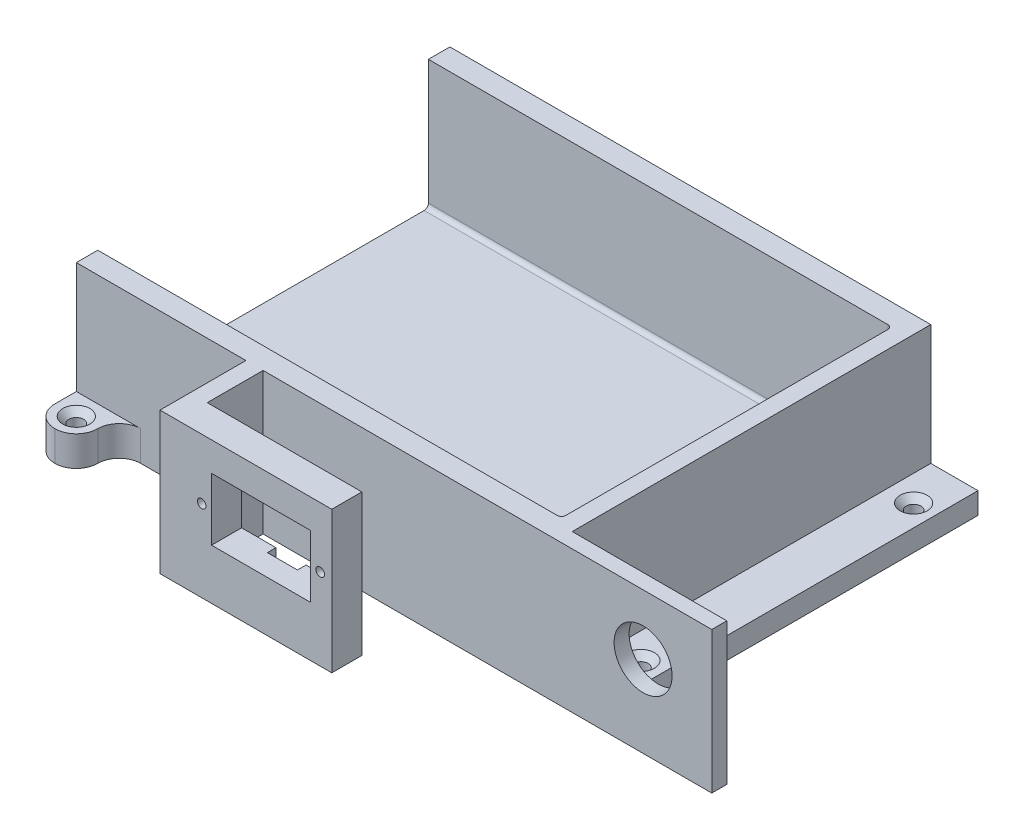
SolidWorks part; units mm, degrees
ref_plane "Plan de face" through (0, 0, 0) normal (0, 0, 1) x (1, 0, 0)
ref_plane "Plan de dessus" through (0, 0, 0) normal (0, 1, 0) x (1, 0, 0)
ref_plane "Plan de droite" through (0, 0, 0) normal (1, 0, 0) x (0, 0, -1)
sketch "Esquisse1" plane through (0, 0, 0) normal (0, 1, 0) x (1, 0, 0)
  line L1 (0, 0) -> (138, 0)
  line L2 (0, 0) -> (0, 77)
  line L3 (0, 77) -> (138, 77)
  line L4 (138, 0) -> (138, 77)
  dimension "D1" = 138
  dimension "D2" = 77
extrude "Boss.-Extru.1" add sketch "Esquisse1" along normal blind 3
sketch "Esquisse2" plane through (0, 3, 0) normal (0, 1, 0) x (1, 0, 0)
  line L0 (0, 0) -> (138, 0) construction
  line L6 (138, 77) -> (123, 77)
  line L7 (138, 77) -> (138, 0)
  line L8 (138, 0) -> (123, 0)
  line L9 (123, 77) -> (123, 0)
  dimension "D1" = 15
extrude "Boss.-Extru.2" add sketch "Esquisse2" along normal blind 30
fillet "Congé1" radius 13.85 1 edges at (123, 3, -38.5)
sketch "Esquisse3" plane through (0, 0, -77) normal (0, 0, -1) x (-1, 0, 0)
  line L0 (-138, 33) -> (-123, 33) construction
  line L1 (-138, 0) -> (0, 0)
  line L2 (-138, 0) -> (-138, 33)
  line L3 (-138, 33) -> (0, 33)
  line L4 (0, 0) -> (0, 33)
extrude "Boss.-Extru.3" add sketch "Esquisse3" along normal blind 5
ref_plane "Plan1" through (0, 0, -38.5) normal (0, 0, 1) x (1, 0, 0)
mirror "Symétrie1" about plane through (0, 0, -38.5) normal (0, 0, 1) of "Boss.-Extru.3"
sketch "Esquisse26" plane through (0, 0, 5) normal (0, 0, 1) x (1, 0, 0)
  line L0 (0, 33) -> (138, 33) construction
  line L1 (0, 0) -> (15, 0)
  line L2 (0, 0) -> (0, 33)
  line L3 (0, 33) -> (15, 33)
  line L4 (15, 0) -> (15, 33)
  dimension "D1" = 15
extrude "Enlèv. mat.-Extru.13" cut sketch "Esquisse26" against normal up to surface (87 mm away) up to face at (69, 16.5, -82)
fillet "Congé5" radius 1 6 edges at (123, 24.925, 0) (118.9434, 7.0566, 0) (123, 24.925, -77) (118.9434, 7.0566, -77) (62.075, 3, 0) (62.075, 3, -77)
sketch "Esquisse27" plane through (0, 0, 5) normal (0, 0, 1) x (1, 0, 0)
  line L0 (138, 0) -> (15, 0) construction
  line L1 (15, 33) -> (19, 33)
  line L2 (15, 33) -> (15, 0)
  line L3 (15, 0) -> (19, 0)
  line L4 (19, 33) -> (19, 0)
  dimension "D1" = 4
extrude "Boss.-Extru.6" [suppressed] add sketch "Esquisse27" along normal blind 34
sketch "Esquisse28" plane through (0, 0, 0) normal (0, -1, 0) x (1, 0, 0)
  line L1 (15, 5) -> (19, 5)
  line L2 (15, 5) -> (15, 48.5)
  line L3 (15, 48.5) -> (39, 48.5)
  line L4 (19, 5) -> (19, 45)
  line L7 (19, 45) -> (39, 45)
  line L8 (39, 48.5) -> (39, 45)
  dimension "D1" = 43.5
  dimension "D2" = 3.5
  dimension "D3" = 20
  dimension "D4" = 4
extrude "Boss.-Extru.7" [suppressed] add sketch "Esquisse28" against normal blind 33
sketch "Esquisse29" [suppressed] plane through (0, 0, 48.5) normal (0, 0, 1) x (1, 0, 0)
  line L0 (39, 33) -> (39, 0) construction
  line L2 (39, 0) -> (15, 0) construction
  line L3 (15, 33) -> (138, 33) construction
  circle A0 centre (29, 19) radius 6
  dimension "D1" = 12
  dimension "D2" = 10
  dimension "D3" = 19
extrude "Enlèv. mat.-Extru.14" [suppressed] cut sketch "Esquisse29" against normal up to surface (3.5 mm away)
sketch "Esquisse33" plane through (0, 33, 0) normal (0, 1, 0) x (1, 0, 0)
  line L0 (15, -5) -> (138, -5) construction
  line L1 (138, 82) -> (127, 82)
  line L2 (138, 82) -> (138, -1.5)
  line L3 (138, -1.5) -> (127, -1.5)
  line L4 (127, 82) -> (127, -1.5)
  line L5 (123, 76) -> (123, 1) construction
  dimension "D1" = 3.5
  dimension "D2" = 4
extrude "Enlèv. mat.-Extru.15" cut sketch "Esquisse33" against normal offset from surface (28 mm away) 5 up to face at (76.5, 0, -38.5)
sketch "Esquisse34" plane through (138, 0, 0) normal (1, 0, 0) x (0, 0, -1)
  line L0 (-1.5, 5) -> (-1.5, 33) construction
  line L1 (-1.5, 0) -> (-5, 0)
  line L2 (-1.5, 0) -> (-1.5, 33)
  line L3 (-1.5, 33) -> (-5, 33)
  line L4 (-5, 0) -> (-5, 33)
extrude "Boss.-Extru.8" add sketch "Esquisse34" along normal blind 25
sketch "Esquisse43" plane through (0, 0, 0) normal (0, -1, 0) x (1, 0, 0)
  line L0 (163, 5) -> (15, 5) construction
  line L1 (54.5, 5) -> (58.5, 5)
  line L2 (54.5, 5) -> (54.5, 25)
  line L3 (54.5, 25) -> (94.5, 25)
  line L4 (58.5, 5) -> (58.5, 18)
  line L5 (15, -82) -> (15, 5) construction
  line L8 (58.5, 18) -> (94.5, 18)
  line L9 (94.5, 25) -> (94.5, 18)
  point P1 (56.5, 5)
  dimension "D1" = 4
  dimension "D2" = 20
  dimension "D3" = 7
  dimension "D4" = 36
  dimension "D5" = 41.5
extrude "Boss.-Extru.11" add sketch "Esquisse43" against normal up to surface (33 mm away) up to face at (94.2012, 33, -31.8333)
sketch "Esquisse35" plane through (0, 0, 25) normal (0, 0, 1) x (1, 0, 0)
  line L1 (66.5, 26.25) -> (89.5, 26.25)
  line L2 (66.5, 26.25) -> (66.5, 11.75)
  line L3 (66.5, 11.75) -> (89.5, 11.75)
  line L4 (89.5, 26.25) -> (89.5, 11.75)
  line L5 (94.5, 33) -> (94.5, 0) construction
  line L7 (94.5, 0) -> (54.5, 0) construction
  circle A0 centre (91.8, 19) radius 1
  circle A1 centre (64.2, 19) radius 1
  point P4 (89.5, 19)
  dimension "D8" = 2
  dimension "D9" = 2
  dimension "D1" = 5
  dimension "D2" = 23
  dimension "D3" = 14.5
  dimension "D4" = 2.3
  dimension "D5" = 7.25
  dimension "D6" = 2.3
  dimension "D7" = 7.25
  dimension "D10" = 19
extrude "Enlèv. mat.-Extru.16" cut sketch "Esquisse35" against normal up to surface (7 mm away) up to face at (76.5, 16.5, 18)
sketch "Esquisse36" plane through (0, 0, 18) normal (0, 0, -1) x (-1, 0, 0)
  line L0 (-89.5, 11.75) -> (-66.5, 11.75) construction
  line L1 (-81.5, 11.75) -> (-74.5, 11.75)
  line L2 (-81.5, 11.75) -> (-81.5, 0)
  line L3 (-81.5, 0) -> (-74.5, 0)
  line L4 (-74.5, 11.75) -> (-74.5, 0)
  line L5 (-89.5, 26.25) -> (-89.5, 11.75) construction
  line L6 (-163, 0) -> (-138, 0) construction
  dimension "D1" = 8
  dimension "D2" = 7
extrude "Enlèv. mat.-Extru.17" cut sketch "Esquisse36" against normal blind 2
sketch "Esquisse44" plane through (0, 0, 5) normal (0, 0, 1) x (1, 0, 0)
  line L0 (58.5, 33) -> (163, 33) construction
  line L1 (163, 33) -> (163, 0) construction
  circle A0 centre (147, 19) radius 6
  dimension "D2" = 12
  dimension "D1" = 14
  dimension "D3" = 16
extrude "Enlèv. mat.-Extru.19" cut sketch "Esquisse44" against normal up to surface (3.5 mm away) up to face at (142.6667, 12.6667, 1.5)
hole_wizard "Dégagement M124" positions "Esquisse47" profile "Esquisse46" hole size "M12" standard "ISO"
sketch "Esquisse47" plane through (0, 0, 5) normal (0, 0, 1) x (1, 0, 0)
  point P0 (147, 19)
sketch "Esquisse46" plane through (147, 19, 5) normal (1, 0, 0) x (0, -1, 0)
  line L0 (0, 0) -> (0, 7.5558)
  line L1 (0, 7.5558) -> (6.75, 3.5)
  line L2 (6.75, 3.5) -> (6.75, 0)
  line L5 (6.75, 0) -> (0, 0)
  line L10 (0, 7.5558) -> (-6.75, 3.5) construction
  line L11 (0, -6.35) -> (0, 107.95) construction
  dimension "Diamètre du perçage" = 13.5
  dimension "Profondeur du perçage" = 3.5
  dimension "Angle de pointe" = 118
sketch "Esquisse48" plane through (0, 5, 0) normal (0, 1, 0) x (1, 0, 0)
  line L0 (138, -1.5) -> (138, 82) construction
  line L1 (127, -1.5) -> (138, -1.5) construction
  line L2 (138, 82) -> (127, 82) construction
  circle A0 centre (133, 8.5) radius 1.5
  circle A2 centre (133, 72) radius 1.5
  dimension "D1" = 3
  dimension "D3" = 3
  dimension "D4" = 5
  dimension "D6" = 5
  dimension "D7" = 10
  dimension "D8" = 10
extrude "Enlèv. mat.-Extru.20" cut sketch "Esquisse48" against normal up to surface (5 mm away) up to face at (84.9375, 0, 1.3125)
hole_wizard "Fraisage pour vis à tête fraisée M32" positions "Esquisse51" profile "Esquisse50" countersink size "M3" standard "ISO"
sketch "Esquisse51" plane through (0, 5, 0) normal (0, 1, 0) x (1, 0, 0)
  point P0 (133, 72)
  point P6 (133, 8.5)
  point P10 (0, 0)
sketch "Esquisse50" plane through (133, 5, -72) normal (1, 0, 0) x (0, 0, 1)
  line L0 (0, 0) -> (0, 6.0215)
  line L1 (0, 6.0215) -> (1.7, 5)
  line L2 (1.7, 5) -> (1.7, 1.45)
  line L3 (1.7, 1.45) -> (3.15, 0)
  line L5 (3.15, 0) -> (0, 0)
  line L6 (-1.7, 1.45) -> (-3.15, 0) construction
  line L10 (0, 6.0215) -> (-1.7, 5) construction
  line L11 (0, -6.35) -> (0, 107.95) construction
  dimension "Diamètre du perçage" = 3.4
  dimension "Profondeur du perçage" = 5
  dimension "Diamètre du fraisage entrant" = 6.3
  dimension "Angle du fraisage entrant" = 90
  dimension "Angle de pointe" = 118
sketch "Esquisse37" plane through (15, 0, 0) normal (-1, 0, 0) x (0, 0, 1)
  line L0 (-82, 0) -> (5, 0) construction
  line L1 (-77, 0) -> (-107, 0)
  line L2 (-77, 0) -> (-77, 68)
  line L3 (-77, 68) -> (-107, 68)
  line L4 (-107, 0) -> (-107, 68)
  line L5 (-77, 4) -> (-77, 33) construction
  line L6 (-82, 33) -> (-77, 33) construction
  dimension "D1" = 30
  dimension "D2" = 35
extrude "Boss.-Extru.9" [suppressed] add sketch "Esquisse37" against normal blind 3.5
sketch "Esquisse38" [suppressed] plane through (15, 0, 0) normal (-1, 0, 0) x (0, 0, 1)
  line L0 (-77, 68) -> (-107, 68) construction
  line L1 (-107, 68) -> (-107, 0) construction
  circle A0 centre (-94.5, 54) radius 6
  dimension "D3" = 12
  dimension "D1" = 14
  dimension "D2" = 12.5
extrude "Enlèv. mat.-Extru.18" [suppressed] cut sketch "Esquisse38" against normal up to surface (3.5 mm away)
hole_wizard "Dégagement M122" [suppressed] positions "Esquisse30" profile "Esquisse32" hole size "M12" standard "ISO"
sketch "Esquisse30" [suppressed] plane through (0, 0, 48.5) normal (0, 0, 1) x (1, 0, 0)
  point P0 (29, 19)
sketch "Esquisse32" plane through (29, 19, 48.5) normal (1, 0, 0) x (0, -1, 0)
  line L0 (0, 0) -> (0, 7.5558)
  line L1 (0, 7.5558) -> (6.75, 3.5)
  line L2 (6.75, 3.5) -> (6.75, 0)
  line L5 (6.75, 0) -> (0, 0)
  line L10 (0, 7.5558) -> (-6.75, 3.5) construction
  line L11 (0, -6.35) -> (0, 107.95) construction
  dimension "Diamètre du perçage" = 13.5
  dimension "Profondeur du perçage" = 3.5
  dimension "Angle de pointe" = 118
hole_wizard "Dégagement M123" [suppressed] positions "Esquisse39" profile "Esquisse40" hole size "M12" standard "ISO"
sketch "Esquisse39" [suppressed] plane through (15, 0, 0) normal (-1, 0, 0) x (0, 0, 1)
  point P0 (-94.5, 54)
sketch "Esquisse40" plane through (15, 54, -94.5) normal (0, 1, 0) x (0, 0, 1)
  line L0 (0, 0) -> (0, 7.5558)
  line L1 (0, 7.5558) -> (6.75, 3.5)
  line L2 (6.75, 3.5) -> (6.75, 0)
  line L5 (6.75, 0) -> (0, 0)
  line L10 (0, 7.5558) -> (-6.75, 3.5) construction
  line L11 (0, -6.35) -> (0, 107.95) construction
  dimension "Diamètre du perçage" = 13.5
  dimension "Profondeur du perçage" = 3.5
  dimension "Angle de pointe" = 118
sketch "Esquisse42" [suppressed] plane through (0, 0, 0) normal (0, -1, 0) x (1, 0, 0)
  line L0 (18.5, -107) -> (18.5, -82)
  line L1 (18.5, -107) -> (28.5, -107)
  line L2 (18.5, -82) -> (28.5, -82)
  line L3 (28.5, -107) -> (28.5, -82)
  dimension "D1" = 10
extrude "Boss.-Extru.10" [suppressed] add sketch "Esquisse42" against normal blind 5
fillet "Congé6" [suppressed] radius 1
fillet "Congé7" [suppressed] radius 10
sketch "Esquisse4" [suppressed] plane through (0, 0, 0) normal (-1, 0, 0) x (0, 0, 1)
  line L1 (0, 33) -> (-25, 33)
  line L2 (0, 33) -> (0, 13)
  line L3 (0, 13) -> (-25, 13)
  line L4 (-25, 33) -> (-25, 13)
  dimension "D1" = 25
  dimension "D2" = 20
extrude "Enlèv. mat.-Extru.1" [suppressed] cut sketch "Esquisse4" against normal blind 6
sketch "Esquisse5" [suppressed] plane through (0, 33, 0) normal (0, 1, 0) x (1, 0, 0)
  line L0 (123, 76) -> (123, 1) construction
  line L1 (138, 82) -> (128, 82)
  line L2 (138, 82) -> (138, 3.5)
  line L3 (138, 3.5) -> (128, 3.5)
  line L4 (128, 82) -> (128, 3.5)
  line L5 (113, 0) -> (138, 0) construction
  dimension "D1" = 5
  dimension "D2" = 3.5
extrude "Enlèv. mat.-Extru.2" [suppressed] cut sketch "Esquisse5" against normal blind 30
sketch "Esquisse6" [suppressed] plane through (0, 0, 0) normal (0, 0, 1) x (1, 0, 0)
  line L0 (113, 33) -> (138, 33) construction
  line L3 (138, 33) -> (138, 0) construction
  circle A0 centre (125.5, 21) radius 6.25
  dimension "D3" = 12.5
  dimension "D1" = 12
  dimension "D2" = 12.5
extrude "Enlèv. mat.-Extru.3" [suppressed] cut sketch "Esquisse6" against normal up to surface (3.5 mm away)
sketch "Esquisse7" [suppressed] plane through (0, 0, -80) normal (0, 0, -1) x (-1, 0, 0)
  line L1 (-138, 0) -> (-118, 0)
  line L2 (-138, 0) -> (-138, 3)
  line L3 (-138, 3) -> (-118, 3)
  line L4 (-118, 0) -> (-118, 3)
extrude "Enlèv. mat.-Extru.4" [suppressed] cut sketch "Esquisse7" against normal blind 30
sketch "Esquisse8" [suppressed] plane through (0, 33, 0) normal (0, 1, 0) x (1, 0, 0)
  line L0 (99.15, 0) -> (99.15, 75) construction
  line L1 (118, 80) -> (99.15, 80)
  line L2 (118, 80) -> (118, 50)
  line L3 (118, 50) -> (99.15, 50)
  line L4 (99.15, 80) -> (99.15, 50)
  dimension "D1" = 30
extrude "Enlèv. mat.-Extru.5" [suppressed] cut sketch "Esquisse8" against normal up to surface (33 mm away)
sketch "Esquisse10" [suppressed] plane through (118, 0, 0) normal (1, 0, 0) x (0, 0, -1)
  line L0 (50, 3) -> (3.5, 3) construction
  line L1 (15.5, 3) -> (23.5, 3)
  line L2 (15.5, 3) -> (15.5, 18)
  line L3 (15.5, 18) -> (23.5, 18)
  line L4 (23.5, 3) -> (23.5, 18)
  dimension "D1" = 12
  dimension "D2" = 8
  dimension "D3" = 15
extrude "Enlèv. mat.-Extru.6" [suppressed] cut sketch "Esquisse10" against normal offset from surface (3 mm away) 2
sketch "Esquisse11" [suppressed] plane through (0, 3, 0) normal (0, 1, 0) x (1, 0, 0)
  line L1 (115, 23.5) -> (118, 23.5)
  line L2 (115, 23.5) -> (115, 15.5)
  line L3 (115, 15.5) -> (131, 15.5)
  line L8 (138, 3.5) -> (131, 3.5)
  line L9 (131, 15.5) -> (131, 3.5)
  line L10 (138, 50) -> (138, 3.5)
  line L11 (118, 50) -> (138, 50)
  line L12 (118, 50) -> (118, 23.5)
  dimension "D1" = 12
  dimension "D2" = 7
  dimension "D3" = 20
extrude "Enlèv. mat.-Extru.7" [suppressed] cut sketch "Esquisse11" against normal up to surface (3 mm away)
sketch "Esquisse12" [suppressed] plane through (0, 0, 0) normal (-1, 0, 0) x (0, 0, 1)
  line L1 (-80, 33) -> (0, 33)
  line L2 (-80, 33) -> (-80, 0)
  line L3 (-80, 0) -> (0, 0)
  line L4 (0, 33) -> (0, 0)
extrude "Enlèv. mat.-Extru.8" [suppressed] cut sketch "Esquisse12" against normal blind 2
sketch "Esquisse13" [suppressed] plane through (0, 0, 0) normal (0, 0, 1) x (1, 0, 0)
  line L0 (37, 0) -> (44.5969, -20)
  line L1 (2, 0) -> (138, 0) construction
  line L2 (44.5969, -20) -> (71.5969, -20)
  line L3 (71.5969, -20) -> (78, 0)
  line L4 (78, 0) -> (37, 0)
  line L7 (113, 33) -> (113, 16.85) construction
  dimension "D1" = 35
  dimension "D2" = 27
  dimension "D3" = 35
  dimension "D4" = 20
  dimension "D5" = 21
extrude "Boss.-Extru.4" [suppressed] add sketch "Esquisse13" against normal blind 7
sketch "Esquisse14" [suppressed] plane through (0, 0, 0) normal (0, 0, 1) x (1, 0, 0)
  line L0 (44.5969, -20) -> (71.5969, -20) construction
  line L1 (46.5, -2.5) -> (69.5, -2.5)
  line L2 (46.5, -2.5) -> (46.5, -17)
  line L3 (46.5, -17) -> (69.5, -17)
  line L4 (69.5, -2.5) -> (69.5, -17)
  dimension "D1" = 23
  dimension "D2" = 9.5
  dimension "D3" = 3
  dimension "D4" = 14.5
extrude "Enlèv. mat.-Extru.9" [suppressed] cut sketch "Esquisse14" against normal up to surface (7 mm away)
fillet "Congé2" [suppressed] radius 10
sketch "Esquisse15" [suppressed] plane through (2, 0, 0) normal (-1, 0, 0) x (0, 0, 1)
  line L0 (0, 33) -> (-80, 33) construction
  line L1 (-42.9875, 33) -> (-35.9875, 33)
  line L2 (-42.9875, 33) -> (-42.9875, 13)
  line L3 (-42.9875, 13) -> (-35.9875, 13)
  line L4 (-35.9875, 33) -> (-35.9875, 13)
  dimension "D1" = 20
  dimension "D2" = 7
extrude "Boss.-Extru.5" [suppressed] add sketch "Esquisse15" along normal blind 45
sketch "Esquisse16" [suppressed] plane through (0, 0, -35.9875) normal (0, 0, 1) x (1, 0, 0)
  line L0 (-20.5, 33) -> (-20.5, 13) construction
  line L1 (-43, 33) -> (2, 33) construction
  line L2 (-43, 13) -> (2, 13) construction
  line L3 (-43, 23) -> (2, 23) construction
  line L4 (-43, 13) -> (-43, 33) construction
  line L5 (2, 13) -> (2, 33) construction
  line L7 (-38, 30.5) -> (-15, 30.5)
  line L8 (-38, 30.5) -> (-38, 16)
  line L9 (-38, 16) -> (-15, 16)
  line L10 (-15, 30.5) -> (-15, 16)
  dimension "D1" = 23
  dimension "D2" = 14.5
  dimension "D3" = 2.5
  dimension "D4" = 5
extrude "Enlèv. mat.-Extru.10" [suppressed] cut sketch "Esquisse16" against normal up to surface (7 mm away)
fillet "Congé3" [suppressed] radius 20
fillet "Congé4" [suppressed] radius 2
sketch "Esquisse18" [suppressed] plane through (0, 0, -42.9875) normal (0, 0, -1) x (-1, 0, 0)
  line L0 (15, 16) -> (38, 16) construction
  line L1 (23, 16) -> (30, 16)
  line L2 (23, 16) -> (23, 13)
  line L3 (23, 13) -> (30, 13)
  line L4 (30, 16) -> (30, 13)
  line L6 (41, 13) -> (-2, 13) construction
  dimension "D1" = 8
  dimension "D2" = 8
extrude "Enlèv. mat.-Extru.11" [suppressed] cut sketch "Esquisse18" against normal blind 2
sketch "Esquisse20" [suppressed] plane through (0, 0, -42.9875) normal (0, 0, -1) x (-1, 0, 0)
  line L0 (38, 30.5) -> (15, 30.5) construction
  line L1 (10.4, 25.9) -> (15, 25.9)
  line L2 (10.4, 25.9) -> (10.4, 20.6)
  line L3 (10.4, 20.6) -> (15, 20.6)
  line L4 (15, 25.9) -> (15, 20.6)
  line L5 (38, 25.9) -> (42.6, 25.9)
  line L6 (38, 25.9) -> (38, 20.6)
  line L7 (38, 20.6) -> (42.6, 20.6)
  line L8 (42.6, 25.9) -> (42.6, 20.6)
  line L9 (15, 16) -> (23, 16) construction
  line L10 (15, 30.5) -> (15, 16) construction
  line L11 (38, 16) -> (38, 30.5) construction
  line L12 (30, 16) -> (38, 16) construction
  dimension "D1" = 4.6
  dimension "D2" = 4.6
  dimension "D3" = 4.6
  dimension "D4" = 4.6
  dimension "D5" = 4.6
  dimension "D6" = 4.6
sketch "Esquisse21" [suppressed] plane through (0, 0, -42.9875) normal (0, 0, -1) x (-1, 0, 0)
  line L0 (15, 25.9) -> (15, 20.6) construction
  line L1 (10.4, 25.9) -> (10.4, 20.6) construction
  line L2 (10.4, 23.25) -> (15, 23.25) construction
  line L3 (15, 23.25) -> (42.6, 23.25) construction
  line L4 (42.6, 25.9) -> (42.6, 20.6) construction
  circle A0 centre (12.7, 23.25) radius 1
  circle A1 centre (40.3, 23.25) radius 1
  dimension "D1" = 2
  dimension "D3" = 2
  dimension "D2" = 2.3
extrude "Enlèv. mat.-Extru.12" [suppressed] cut sketch "Esquisse21" against normal up to surface (7 mm away)
hole_wizard "Dégagement M21" [suppressed] positions "Esquisse22" profile "Esquisse23" hole size "M2" standard "ISO"
sketch "Esquisse22" [suppressed] plane through (0, 0, -42.9875) normal (0, 0, -1) x (-1, 0, 0)
  point P0 (40.3, 23.25)
  point P3 (12.7, 23.25)
sketch "Esquisse23" plane through (-40.3, 23.25, -42.9875) normal (1, 0, 0) x (0, 1, 0)
  line L0 (0, 0) -> (0, 10.721)
  line L1 (0, 10.721) -> (1.2, 10)
  line L2 (1.2, 10) -> (1.2, 0)
  line L5 (1.2, 0) -> (0, 0)
  line L10 (0, 10.721) -> (-1.2, 10) construction
  line L11 (0, -6.35) -> (0, 107.95) construction
  dimension "Diamètre du perçage" = 2.4
  dimension "Profondeur du perçage" = 10
  dimension "Angle de pointe" = 118
hole_wizard "Dégagement M121" [suppressed] positions "Esquisse24" profile "Esquisse25" hole size "M12" standard "ISO"
sketch "Esquisse24" [suppressed] plane through (0, 0, 0) normal (0, 0, 1) x (1, 0, 0)
  point P0 (125.5, 21)
sketch "Esquisse25" plane through (125.5, 21, 0) normal (1, 0, 0) x (0, -1, 0)
  line L0 (0, 0) -> (0, 14.0558)
  line L1 (0, 14.0558) -> (6.75, 10)
  line L2 (6.75, 10) -> (6.75, 0)
  line L5 (6.75, 0) -> (0, 0)
  line L10 (0, 14.0558) -> (-6.75, 10) construction
  line L11 (0, -6.35) -> (0, 107.95) construction
  dimension "Diamètre du perçage" = 13.5
  dimension "Profondeur du perçage" = 10
  dimension "Angle de pointe" = 118
sketch "Esquisse52" plane through (0, 0, 0) normal (0, -1, 0) x (1, 0, 0)
  line L0 (54.5, 5) -> (15, 5) construction
  line L1 (15, 5) -> (25, 5)
  line L2 (15, 5) -> (15, 15)
  line L3 (15, 15) -> (25, 15)
  line L4 (25, 5) -> (25, 15)
  line L6 (15, -82) -> (15, 5) construction
  point P6 (15, 5)
  point P9 (23.2289, 13.9624)
  dimension "D1" = 10
  dimension "D2" = 10
extrude "Boss.-Extru.12" add sketch "Esquisse52" against normal blind 7
sketch "Esquisse53" plane through (0, 7, 0) normal (0, 1, 0) x (1, 0, 0)
  line L0 (15, -15) -> (15, -5) construction
  line L1 (25, -15) -> (15, -15) construction
  circle A0 centre (20, -10) radius 1.5
  dimension "D3" = 3
  dimension "D1" = 5
  dimension "D2" = 5
extrude "Enlèv. mat.-Extru.21" cut sketch "Esquisse53" against normal up to surface (7 mm away) up to face at (133, 0, -10.2)
hole_wizard "Fraisage pour vis à tête fraisée M33" positions "Esquisse54" profile "Esquisse55" countersink size "M3" standard "ISO"
sketch "Esquisse54" plane through (0, 7, 0) normal (0, 1, 0) x (1, 0, 0)
  point P0 (20, -10)
sketch "Esquisse55" plane through (20, 7, 10) normal (1, 0, 0) x (0, 0, 1)
  line L0 (0, 0) -> (0, 8.0215)
  line L1 (0, 8.0215) -> (1.7, 7)
  line L2 (1.7, 7) -> (1.7, 1.45)
  line L3 (1.7, 1.45) -> (3.15, 0)
  line L5 (3.15, 0) -> (0, 0)
  line L6 (-1.7, 1.45) -> (-3.15, 0) construction
  line L10 (0, 8.0215) -> (-1.7, 7) construction
  line L11 (0, -6.35) -> (0, 107.95) construction
  dimension "Diamètre du perçage" = 3.4
  dimension "Profondeur du perçage" = 7
  dimension "Diamètre du fraisage entrant" = 6.3
  dimension "Angle du fraisage entrant" = 90
  dimension "Angle de pointe" = 118
mirror "Symétrie2" about plane through (0, 0, -38.5) normal (0, 0, 1) of "Fraisage pour vis à tête fraisée M33", "Enlèv. mat.-Extru.21", "Boss.-Extru.12"
fillet "Congé8" radius 5 6 edges at (25, 3.5, 5) (25, 3.5, 15) (15, 3.5, 15) (15, 3.5, -92) (25, 3.5, -92) (25, 3.5, -82)
